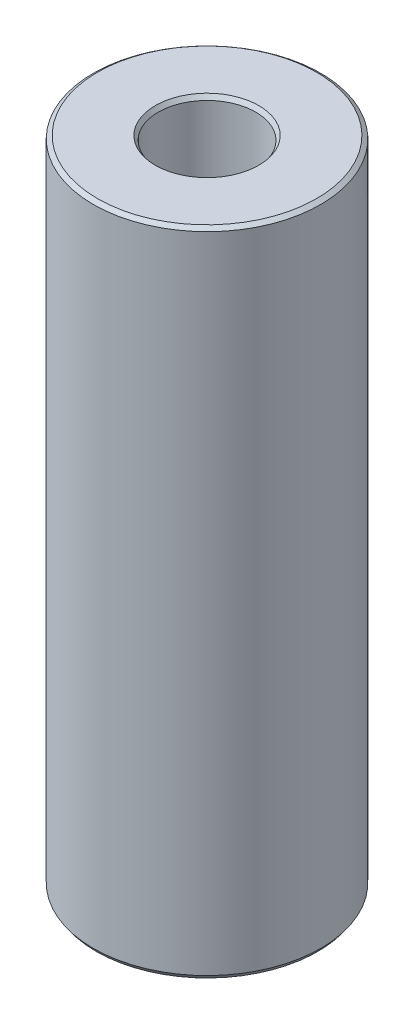
SolidWorks part; units mm, degrees
ref_plane "Front Plane" through (0, 0, 0) normal (0, 0, 1) x (1, 0, 0)
ref_plane "Top Plane" through (0, 0, 0) normal (0, 1, 0) x (1, 0, 0)
ref_plane "Right Plane" through (0, 0, 0) normal (1, 0, 0) x (0, 0, -1)
sketch "Sketch1" plane through (0, 0, 0) normal (0, 1, 0) x (1, 0, 0)
  circle A0 centre (0, 0) radius 40
  dimension "SLEEVE_OD" = 80
extrude "Boss-Extrude1" add sketch "Sketch1" along normal blind 229.1217
sketch "Sketch2" plane through (0, 0, 0) normal (0, 1, 0) x (1, 0, 0)
  circle A0 centre (0, 0) radius 17.1572
  dimension "BORE_D" = 34.3144
extrude "Cut-Extrude1" cut sketch "Sketch2" along normal through all
chamfer "Chamfer1" distance 1.0443 angle 54.741 4 edges at (0, 229.1217, 17.1572) (0, 0, 17.1572) (0, 0, 40) (0, 229.1217, 40) first distance on face at (0, 229.1217, 17.1572) first distance on face at (0, 0, 17.1572) first distance on face at (0, 229.1217, 40)
